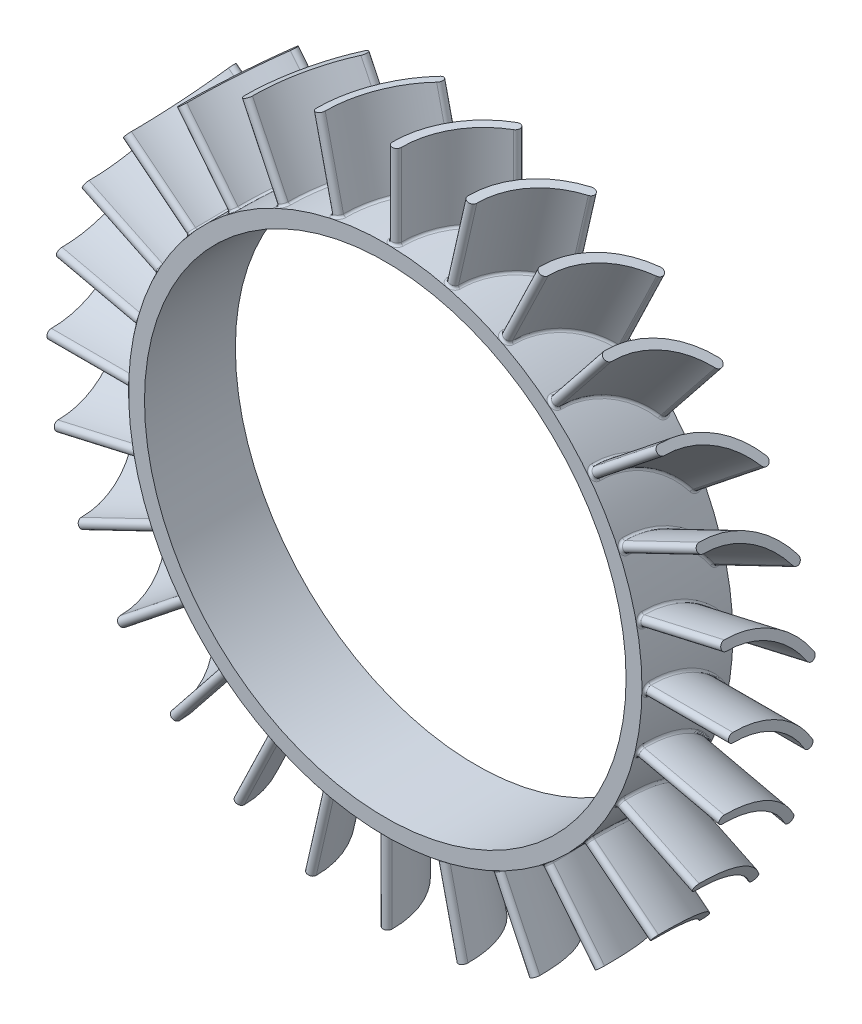
SolidWorks part; units mm, degrees
ref_plane "Front Plane" through (0, 0, 0) normal (0, 0, 1) x (1, 0, 0)
ref_plane "Top Plane" through (0, 0, 0) normal (0, 1, 0) x (1, 0, 0)
ref_plane "Right Plane" through (0, 0, 0) normal (1, 0, 0) x (0, 0, -1)
sketch "Sketch1" plane through (0, 0, 0) normal (0, 0, 1) x (1, 0, 0)
  circle A0 centre (0, 0) radius 53
  circle A1 centre (0, 0) radius 56.5
  dimension "D1" = 106
  dimension "D2" = 113
extrude "Boss-Extrude1" add sketch "Sketch1" along normal mid plane 20
sketch "Sketch2" plane through (0, 0, 0) normal (0, 1, 0) x (1, 0, 0)
  line L0 (53, 10) -> (-53, 10) construction
  line L1 (-56.5, -10) -> (56.5, -10) construction
  arc A0 (0, -8.5) -> (10, 9) centre (19.9992, -8.321) cw
  arc A1 (1.9999, -8.4821) -> (10.9999, 7.2679) centre (19.9992, -8.321) cw
  arc A2 (10, 9) -> (10.9999, 7.2679) centre (10.5, 8.134) cw
  arc A3 (0, -8.5) -> (1.9999, -8.4821) centre (1, -8.491) ccw
  dimension "D4" = 20
  dimension "D1" = 1
  dimension "D2" = 1.5
  dimension "D3" = 10
  dimension "D5" = 2
extrude "Boss-Extrude2" add sketch "Sketch2" along normal blind 20 from offset 55
fillet "Fillet1" radius 0.5 4 edges at (0.8947, 56.4929, 9.4855) (1.5023, 56.48, 0.7142) (9.6041, 55.6777, -7.6896) (2.5298, 56.4433, 3.9826)
pattern_circular "CirPattern1" count 28 over 360 about axis through (0, 0, 10) along (0, 0, -1) of "Fillet1", "Boss-Extrude2"
